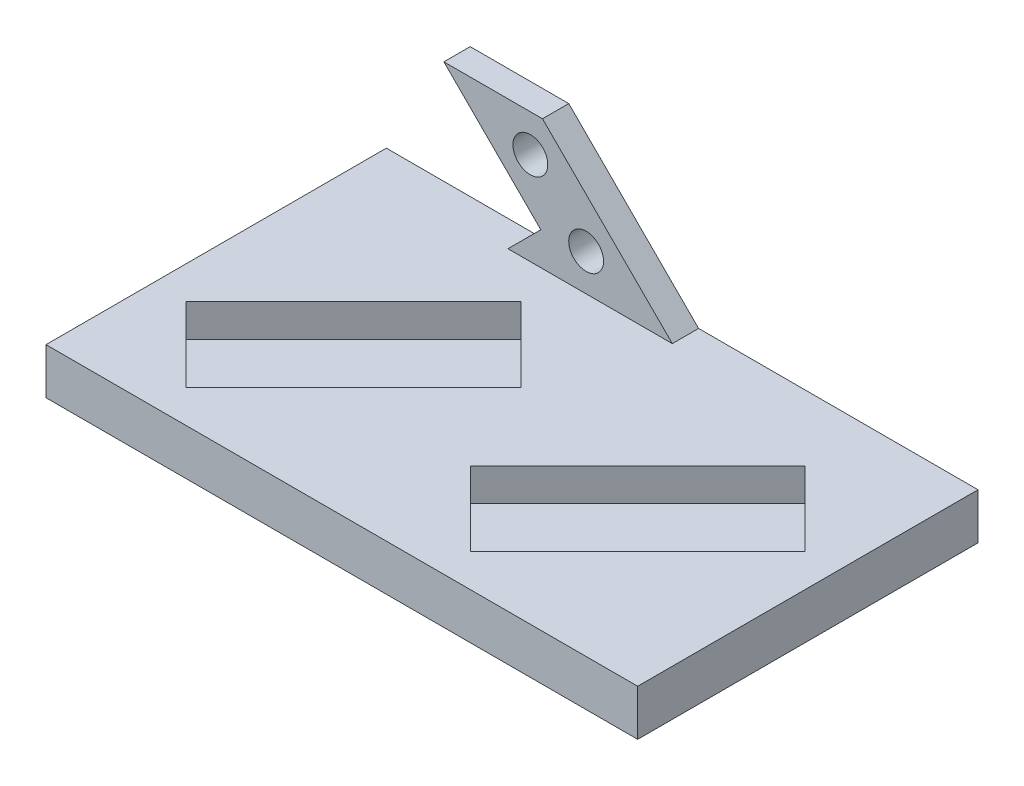
SolidWorks part; units mm, degrees
ref_plane "Front Plane" through (0, 0, 0) normal (0, 0, 1) x (1, 0, 0)
ref_plane "Top Plane" through (0, 0, 0) normal (0, 1, 0) x (1, 0, 0)
ref_plane "Right Plane" through (0, 0, 0) normal (1, 0, 0) x (0, 0, -1)
sketch "Sketch1" plane through (0, 0, 0) normal (0, 1, 0) x (1, 0, 0)
  line L7 (5, -35.4558) -> (16.3137, -46.7696)
  line L8 (0, 0) -> (90, 0)
  line L9 (0, 0) -> (0, -51.7696)
  line L10 (0, -51.7696) -> (90, -51.7696)
  line L11 (90, 0) -> (90, -51.7696)
  line L12 (16.3137, -46.7696) -> (41.7696, -21.3137)
  line L13 (41.7696, -21.3137) -> (30.4558, -10)
  line L14 (30.4558, -10) -> (5, -35.4558)
  line L15 (36.1127, -15.6569) -> (10.6569, -41.1127) construction
  line L16 (17.7279, -22.7279) -> (29.0416, -34.0416) construction
  line L17 (45, 0) -> (45, -51.7696) construction
  line L18 (48.2304, -35.4558) -> (59.5442, -46.7696)
  line L19 (59.5442, -46.7696) -> (85, -21.3137)
  line L20 (85, -21.3137) -> (73.6863, -10)
  line L21 (73.6863, -10) -> (48.2304, -35.4558)
  line L22 (79.3431, -15.6569) -> (53.8873, -41.1127) construction
  point P1 (0, 0)
  dimension "D4" = 36
  dimension "D5" = 16
  dimension "D6" = 45
  dimension "D7" = 5
  dimension "D8" = 5
  dimension "D10" = 36
  dimension "D11" = 16
  dimension "D12" = 5
  dimension "D13" = 5
extrude "Boss-Extrude1" add sketch "Sketch1" along normal blind 5 contours L11 L9 L10 L21 L20 L19 L18 L14 L13 L12 L7 region at (45, 0, 25.0636)
sketch "Sketch5" plane through (0, 0, 0) normal (0, 0, -1) x (-1, 0, 0)
  line L0 (-52.5, 0) -> (-27.7513, 24.7487)
  line L1 (0, 0) -> (-90, 0) construction
  line L2 (-27.7513, 24.7487) -> (-12.7513, 24.7487)
  line L3 (-12.7513, 24.7487) -> (-37.5, 0)
  line L4 (-37.5, 0) -> (-52.5, 0)
  line L5 (-20.2513, 24.7487) -> (-45, 0) construction
  line L6 (-45, 0) -> (-45, 5) construction
  line L7 (0, 5) -> (-90, 5) construction
  circle A0 centre (-25.9081, 19.0919) radius 2.65
  circle A1 centre (-34.3934, 10.6066) radius 2.65
  dimension "D3" = 5.3
  dimension "D1" = 45
  dimension "D2" = 12
  dimension "D4" = 15
  dimension "D5" = 35
  dimension "D6" = 8
extrude "Boss-Extrude2" add sketch "Sketch5" against normal blind 4
chamfer "Chamfer1" distance 10 angle 45 1 edges at (32.5, 5, 2) first distance on face at (42.5, 5, 13.9424)
sketch "Sketch6" plane through (0, 0, 0) normal (0, -1, 0) x (1, 0, 0)
  line L1 (0, 51.7696) -> (90, 51.7696)
  line L2 (0, 51.7696) -> (0, 0)
  line L3 (0, 0) -> (90, 0)
  line L4 (90, 51.7696) -> (90, 0)
extrude "Boss-Extrude3" add sketch "Sketch6" along normal blind 2
